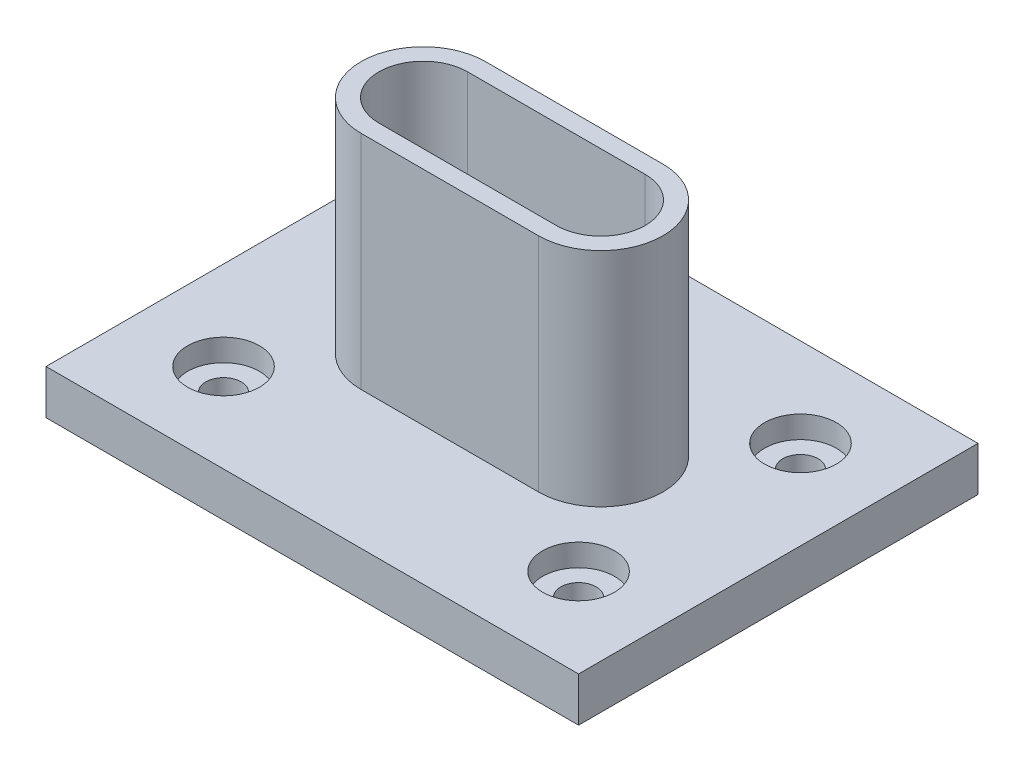
SolidWorks part; units mm, degrees
ref_plane "Front Plane" through (0, 0, 0) normal (0, 0, 1) x (1, 0, 0)
ref_plane "Top Plane" through (0, 0, 0) normal (0, 1, 0) x (1, 0, 0)
ref_plane "Right Plane" through (0, 0, 0) normal (1, 0, 0) x (0, 0, -1)
sketch "Sketch1" plane through (0, 0, 0) normal (0, 1, 0) x (1, 0, 0)
  line L0 (-50.8, -31.75) -> (50.8, -31.75) construction
  line L1 (76.2, -57.15) -> (-76.2, -57.15)
  line L2 (76.2, -57.15) -> (76.2, 57.15)
  line L3 (76.2, 57.15) -> (-76.2, 57.15)
  line L4 (-76.2, -57.15) -> (-76.2, 57.15)
  line L5 (76.2, -57.15) -> (-76.2, 57.15) construction
  line L6 (76.2, 57.15) -> (-76.2, -57.15) construction
  line L7 (-50.8, -31.75) -> (-50.8, 31.75) construction
  line L8 (-25.4, 0) -> (25.4, 0) construction
  line L9 (-25.4, 12.7) -> (25.4, 12.7)
  line L10 (-25.4, -12.7) -> (25.4, -12.7)
  circle A0 centre (-50.8, -31.75) radius 5.08
  circle A1 centre (-50.8, -31.75) radius 10.287
  circle A2 centre (50.8, -31.75) radius 5.08
  circle A3 centre (50.8, -31.75) radius 10.287
  circle A4 centre (50.8, 31.75) radius 5.08
  circle A5 centre (50.8, 31.75) radius 10.287
  circle A6 centre (-50.8, 31.75) radius 5.08
  circle A7 centre (-50.8, 31.75) radius 10.287
  arc A8 (-25.4, 12.7) -> (-25.4, -12.7) centre (-25.4, 0) ccw
  arc A9 (25.4, -12.7) -> (25.4, 12.7) centre (25.4, 0) ccw
  point P0 (0, 0)
  point P23 (0, 0)
  point P28 (0, 0)
  point P36 (0, -23.8656)
  dimension "D3" = 10.16
  dimension "D4" = 20.574
  dimension "D1" = 114.3
  dimension "D2" = 152.4
  dimension "D5" = 25.4
  dimension "D6" = 25.4
  dimension "D9" = 101.6
  dimension "D10" = 63.5
  dimension "D11" = 50.8
  dimension "D12" = 25.4
  dimension "D7" = 2
  dimension "D8" = 2
extrude "Boss-Extrude1" add sketch "Sketch1" against normal blind 12.7 contours L4 L1 L2 L3 A9 L10 A8 L9 A7 A5 A3 A1 region at (0, 0, 55.245)
extrude "Extrude-Thin1" add sketch "Sketch1<3>" along normal blind 63.5 thin contours L9 A9 L10 A8 thin type one direction wall 5.08
sketch "Sketch1<3>" plane through (0, 0, 0) normal (0, 1, 0) x (1, 0, 0) same geometry as "Sketch1"
extrude "Boss-Extrude2" add sketch "Sketch1<4>" against normal up to surface (12.7 mm away) contours A7 A6 | A1 A0 | A3 A2 | A5 A4 region at (-60.796, 0, 31.75) region at (40.804, 0, 31.75) region at (40.804, 0, -31.75) region at (-60.796, 0, -31.75) up to face at (0, -12.7, 0)
sketch "Sketch1<4>" plane through (0, 0, 0) normal (0, 1, 0) x (1, 0, 0) same geometry as "Sketch1"
extrude "Cut-Extrude1" cut sketch "Sketch1<5>" against normal blind 6.35 contours A1 A0 | A7 A6 | A5 A4 | A3 A2 region at (-60.796, 0, 31.75) region at (40.804, 0, 31.75) region at (40.804, 0, -31.75) region at (-60.796, 0, -31.75)
sketch "Sketch1<5>" plane through (0, 0, 0) normal (0, 1, 0) x (1, 0, 0) same geometry as "Sketch1"
